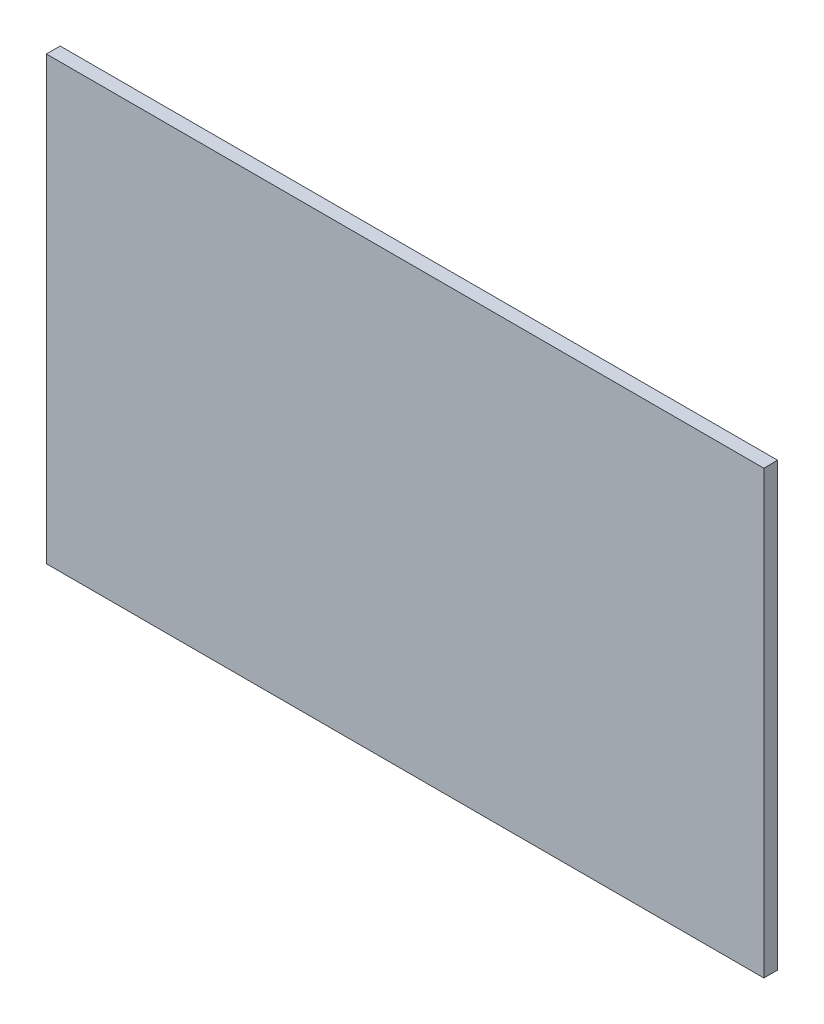
SolidWorks part; units mm, degrees
material "ALUMINUM 6061-T6"
ref_plane "Front Plane" through (0, 0, 0) normal (0, 0, 1) x (1, 0, 0)
ref_plane "Top Plane" through (0, 0, 0) normal (0, 1, 0) x (1, 0, 0)
ref_plane "Right Plane" through (0, 0, 0) normal (1, 0, 0) x (0, 0, -1)
sketch "Sketch1" plane through (0, 0, 0) normal (0, 0, 1) x (1, 0, 0)
  line L1 (-165.1, -101.6) -> (165.1, -101.6)
  line L2 (-165.1, -101.6) -> (-165.1, 101.6)
  line L3 (-165.1, 101.6) -> (165.1, 101.6)
  line L4 (165.1, -101.6) -> (165.1, 101.6)
  line L5 (-165.1, -101.6) -> (165.1, 101.6) construction
  line L6 (-165.1, 101.6) -> (165.1, -101.6) construction
  point P0 (0, 0)
  dimension "D1" = 330.2
  dimension "D2" = 203.2
extrude "Boss-Extrude1" add sketch "Sketch1" along normal mid plane 6.35
